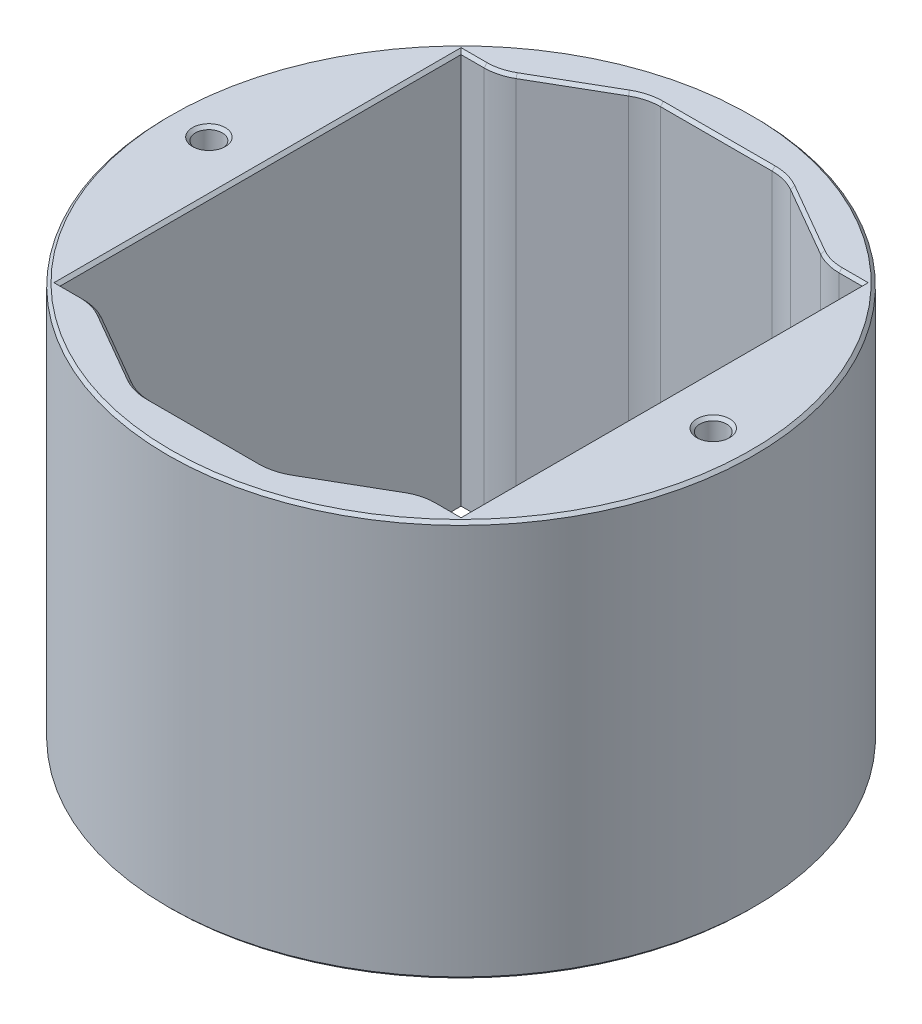
SolidWorks part; units mm, degrees
material "ABS"
ref_plane "Front Plane" through (0, 0, 0) normal (0, 0, 1) x (1, 0, 0)
ref_plane "Top Plane" through (0, 0, 0) normal (0, 1, 0) x (1, 0, 0)
ref_plane "Right Plane" through (0, 0, 0) normal (1, 0, 0) x (0, 0, -1)
sketch "Sketch1" plane through (0, 0, 0) normal (0, 1, 0) x (1, 0, 0)
  circle A0 centre (0, 0) radius 73.787
  dimension "D1" = 147.574
extrude "Boss-Extrude1" add sketch "Sketch1" along normal blind 100 contours A0
sketch "Sketch2" plane through (0, 100, 0) normal (0, 1, 0) x (1, 0, 0)
  line L1 (-50.5, -50.5) -> (50.5, -50.5)
  line L2 (-50.5, -50.5) -> (-50.5, 50.5)
  line L3 (-50.5, 50.5) -> (50.5, 50.5)
  line L4 (50.5, -50.5) -> (50.5, 50.5)
  line L5 (-50.5, -50.5) -> (50.5, 50.5) construction
  line L6 (-50.5, 50.5) -> (50.5, -50.5) construction
  point P0 (0, 0)
  dimension "D1" = 101
  dimension "D2" = 101
extrude "Cut-Extrude1" cut sketch "Sketch2" against normal through all
sketch "Sketch3" plane through (0, 100, 0) normal (0, 1, 0) x (1, 0, 0)
  line L0 (-17.4625, -64.262) -> (17.4625, -64.262)
  line L1 (-50.5, -50.5) -> (50.5, -50.5) construction
  line L2 (-50.5, -50.5) -> (50.5, -50.5) construction
  line L3 (-17.4625, -64.262) -> (-41.299, -50.5)
  line L4 (17.4625, -64.262) -> (41.299, -50.5)
  line L5 (-41.299, -50.5) -> (41.299, -50.5)
  point P4 (0, -50.5)
  point P5 (0, -64.262)
  dimension "D1" = 34.925
  dimension "D2" = 30
  dimension "D3" = 30
  dimension "D4" = 13.762
extrude "Cut-Extrude2" cut sketch "Sketch3" against normal through all
ref_plane "Plane1" through (0, 0, 0) normal (0, 0, -1) x (-1, 0, 0)
mirror "Mirror1" about plane through (0, 0, 0) normal (0, 0, -1) of "Cut-Extrude2"
fillet "Fillet1" radius 12.7 8 edges at (17.4625, 50, 64.262) (41.299, 50, 50.5) (-17.4625, 50, 64.262) (-41.299, 50, 50.5) (41.299, 50, -50.5) (17.4625, 50, -64.262) (-17.4625, 50, -64.262) (-41.299, 50, -50.5)
sketch "Sketch4" plane through (0, 100, 0) normal (0, 1, 0) x (1, 0, 0)
  line L0 (-63.5, 0) -> (63.5, 0) construction
  circle A0 centre (-63.5, 0) radius 3.3782
  circle A1 centre (63.5, 0) radius 3.3782
  point P4 (0, 0)
  dimension "D1" = 63.5
  dimension "D2" = 6.7564
extrude "Cut-Extrude3" cut sketch "Sketch4" against normal through all
chamfer "Chamfer1" distance 0.762 angle 45 46 edges at (17.3465, 0, 63.8293) (0, 0, 64.262) (-17.3465, 0, 63.8293) (-29.3807, 0, 57.381) (-41.4149, 0, 50.9327) (-47.601, 0, 50.5) (-50.5, 0, 0) (-47.601, 0, -50.5) (-41.4149, 0, -50.9327) (-29.3807, 0, -57.381) (-17.3465, 0, -63.8293) (0, 0, -64.262) (17.3465, 0, -63.8293) (29.3807, 0, -57.381) (41.4149, 0, -50.9327) (47.601, 0, -50.5) (50.5, 0, 0) (47.601, 0, 50.5) (41.4149, 0, 50.9327) (29.3807, 0, 57.381) (0, 0, 73.787) (63.5, 0, 3.3782) (-63.5, 0, 3.3782) (50.5, 100, 0) (47.601, 100, -50.5) (41.4149, 100, -50.9327) (29.3807, 100, -57.381) (17.3465, 100, -63.8293) (0, 100, -64.262) (-17.3465, 100, -63.8293) (-29.3807, 100, -57.381) (-41.4149, 100, -50.9327) (-47.601, 100, -50.5) (-50.5, 100, 0) (-47.601, 100, 50.5) (-41.4149, 100, 50.9327) (-29.3807, 100, 57.381) (-17.3465, 100, 63.8293) (0, 100, 64.262) (17.3465, 100, 63.8293) (29.3807, 100, 57.381) (41.4149, 100, 50.9327) (47.601, 100, 50.5) (0, 100, 73.787) (63.5, 100, 3.3782) (-63.5, 100, 3.3782)
